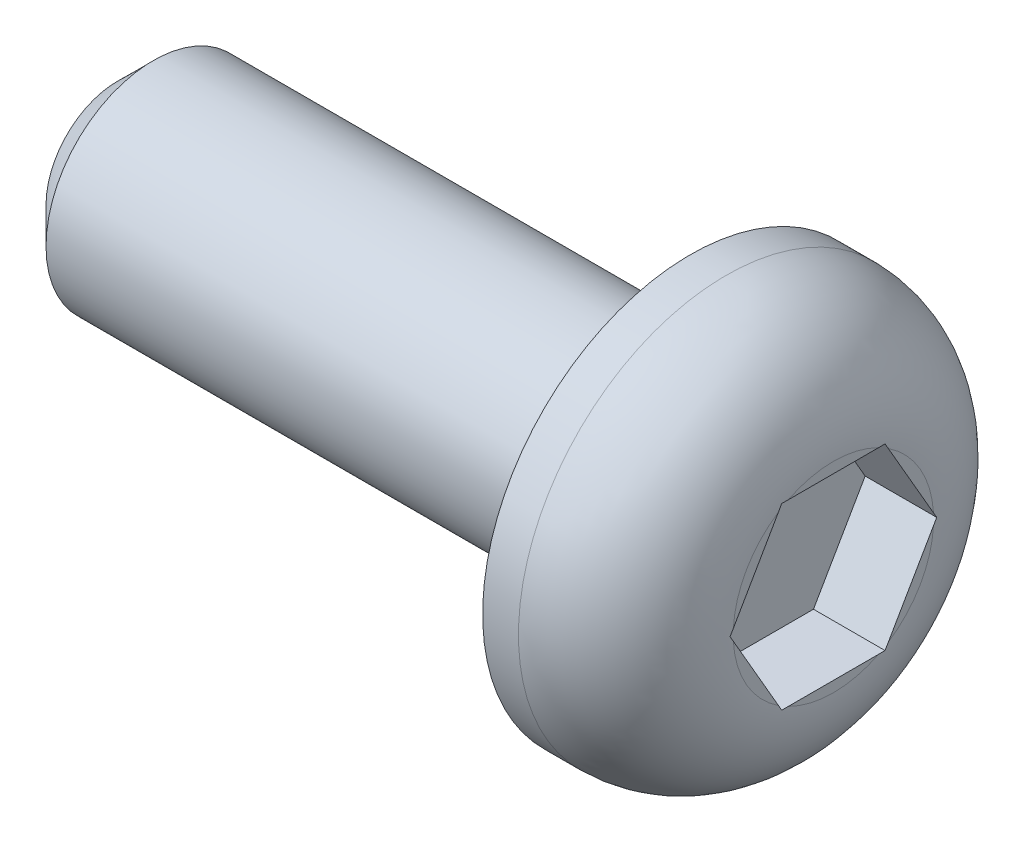
SolidWorks part; units mm, degrees
ref_plane "Front Plane" through (0, 0, 0) normal (0, 0, 1) x (1, 0, 0)
ref_plane "Top Plane" through (0, 0, 0) normal (0, 1, 0) x (1, 0, 0)
ref_plane "Right Plane" through (0, 0, 0) normal (1, 0, 0) x (0, 0, -1)
sketch "Sketch1" plane through (0, 0, 0) normal (0, 1, 0) x (1, 0, 0)
  line L1 (0, 0) -> (-8, 0)
  line L2 (0, 0) -> (0, -1.5)
  line L3 (0, -1.5) -> (-8, -1.5)
  line L4 (-8, 0) -> (-8, -1.5)
  line L5 (0, -1.5) -> (2, -1.5)
  line L6 (0, -1.5) -> (0, 1.4)
  line L7 (0, 1.4) -> (2, 1.4)
  line L8 (2, -1.5) -> (2, 1.4)
  dimension "D1" = 2
  dimension "D2" = 2.9
  dimension "D3" = 1.5
  dimension "D4" = 8
revolve "Revolve1" add sketch "Sketch1" angle 360 about L3 region at (-4, 0, 0.75) region at (1, 0, 0.05)
ref_point "Point1"
sketch "Sketch3" plane through (2, 0, 0) normal (1, 0, 0) x (0, 0, -1)
  line L1 (-2.2217, -1.25) -> (-0.7783, -1.25)
  line L2 (-0.7783, -1.25) -> (-0.0566, 0)
  line L3 (-0.0566, 0) -> (-0.7783, 1.25)
  line L4 (-0.7783, 1.25) -> (-2.2217, 1.25)
  line L5 (-2.2217, 1.25) -> (-2.9434, 0)
  line L6 (-2.9434, 0) -> (-2.2217, -1.25)
  circle A0 centre (-1.5, 0) radius 1.25 construction
  dimension "D1" = 2.5
extrude "Cut-Extrude1" cut sketch "Sketch3" against normal blind 1
fillet "Fillet1" radius 1.5 1 edges at (2, 0, -1.4)
chamfer "Chamfer1" distance 0.5 angle 45 1 edges at (-8, 0, 0)
